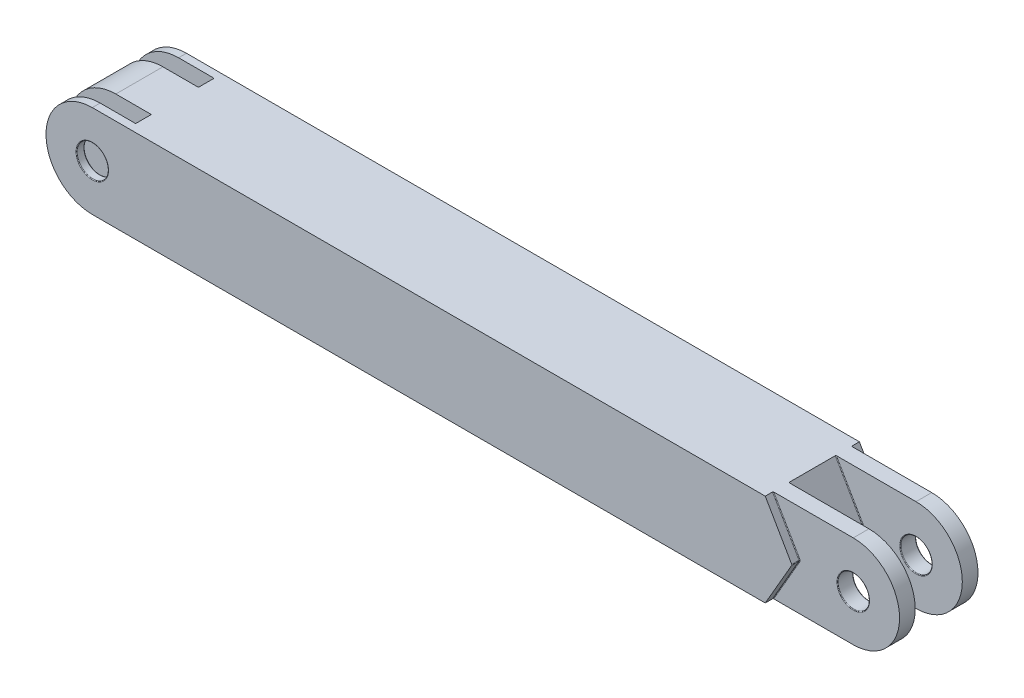
SolidWorks part; units mm, degrees
material "Structural Steel"
ref_plane "Front Plane" through (0, 0, 0) normal (0, 0, 1) x (1, 0, 0)
ref_plane "Top Plane" through (0, 0, 0) normal (0, 1, 0) x (1, 0, 0)
ref_plane "Right Plane" through (0, 0, 0) normal (1, 0, 0) x (0, 0, -1)
sketch "Sketch2" plane through (0, 0, 0) normal (0, 0, 1) x (1, 0, 0)
  line L0 (-3378.4578, 0) -> (441.8552, 0) construction
  line L1 (-2400, 147.5) -> (0, 147.5)
  line L2 (0, -147.5) -> (-2400, -147.5)
  arc A0 (0, 147.5) -> (0, -147.5) centre (0, 0) cw
  arc A1 (-2400, -147.5) -> (-2400, 147.5) centre (-2400, 0) cw
  circle A2 centre (-2400, 0) radius 50
  circle A3 centre (0, 0) radius 50
  dimension "D2" = 147.5
  dimension "D3" = 100
  dimension "D4" = 100
  dimension "D1" = 2400
extrude "Boss-Extrude1" add sketch "Sketch2" along normal mid plane 300
sketch "Sketch4" plane through (0, 0, 0) normal (0, 0, 1) x (1, 0, 0)
  line L0 (-2257.5259, 38.1758) -> (-2286.8193, 147.5)
  line L4 (-3008.6022, 0) -> (749.044, 0) construction
  line L7 (0, 147.5) -> (-2400, 147.5) construction
  line L8 (-2253.0613, 12.8555) -> (-2239.032, -147.5)
  line L9 (-2400, -147.5) -> (0, -147.5) construction
  line L10 (-2286.8193, 147.5) -> (-2400, 147.5)
  line L11 (-2239.032, -147.5) -> (-2400, -147.5)
  arc A0 (-2400, 147.5) -> (-2400, -147.5) centre (-2400, 0) ccw
  arc A1 (-2400, -147.5) -> (-2253.0613, 12.8555) centre (-2400, 0) ccw construction
  arc A2 (-2253.0613, 12.8555) -> (-2257.5259, 38.1758) centre (-2400, 0) ccw
  arc A4 (-2400, 147.5) -> (-2400, -147.5) centre (-2400, 0) ccw construction
  dimension "D1" = 75
  dimension "D2" = 95
extrude "Cut-Extrude1" cut sketch "Sketch4" against normal blind 50 from offset 75 offset against normal yes
mirror "Mirror1" about plane through (0, 0, 0) normal (0, 0, 1) of "Cut-Extrude1"
sketch "Sketch5" plane through (0, 0, 0) normal (0, 0, 1) x (1, 0, 0)
  line L0 (-255.4775, 147.5) -> (-170.3183, 0)
  line L1 (-163.8289, -283.76) -> (104.6936, 181.3346) construction
  line L2 (0, 147.5) -> (-2400, 147.5) construction
  line L4 (-485.1827, 0) -> (365.4599, 0) construction
  line L5 (-170.3183, 0) -> (-255.4775, -147.5)
  line L6 (-2400, -147.5) -> (0, -147.5) construction
  line L7 (-170.3183, 147.5) -> (-170.3183, -147.5) construction
  line L8 (0, 147.5) -> (-255.4775, 147.5)
  line L9 (-255.4775, -147.5) -> (0, -147.5)
  arc A0 (0, -147.5) -> (0, 147.5) centre (0, 0) ccw construction
  arc A3 (0, -147.5) -> (0, 147.5) centre (0, 0) ccw
  dimension "D1" = 147.5
  dimension "D2" = 60
  dimension "D3" = 60
extrude "Cut-Extrude2" cut sketch "Sketch5" against normal mid plane 150
sketch "Sketch6" plane through (0, 0, 150) normal (0, 0, 1) x (1, 0, 0)
  line L4 (-170.3183, 0) -> (-255.4775, -147.5)
  line L5 (0, 147.5) -> (-255.4775, 147.5)
  line L6 (-255.4775, -147.5) -> (0, -147.5)
  line L7 (-170.3183, 0) -> (-255.4775, -147.5)
  line L8 (-255.4775, 147.5) -> (-170.3183, 0)
  line L9 (0, 147.5) -> (-255.4775, 147.5)
  line L10 (-255.4775, -147.5) -> (0, -147.5)
  line L11 (-255.4775, 147.5) -> (-170.3183, 0)
  arc A3 (0, -147.5) -> (0, 147.5) centre (0, 0) ccw
  arc A5 (0, -147.5) -> (0, 147.5) centre (0, 0) ccw
  dimension "D1" = 0
extrude "Cut-Extrude3" cut sketch "Sketch6" against normal blind 25
sketch "Sketch7" plane through (0, 0, -150) normal (0, 0, -1) x (-1, 0, 0)
  line L4 (170.3183, 0) -> (255.4775, 147.5)
  line L5 (0, -147.5) -> (255.4775, -147.5)
  line L6 (255.4775, 147.5) -> (0, 147.5)
  line L7 (170.3183, 0) -> (255.4775, 147.5)
  line L8 (255.4775, -147.5) -> (170.3183, 0)
  line L9 (0, -147.5) -> (255.4775, -147.5)
  line L10 (255.4775, 147.5) -> (0, 147.5)
  line L11 (255.4775, -147.5) -> (170.3183, 0)
  arc A3 (0, 147.5) -> (0, -147.5) centre (0, 0) ccw
  arc A5 (0, 147.5) -> (0, -147.5) centre (0, 0) ccw
  dimension "D1" = 0
extrude "Cut-Extrude4" cut sketch "Sketch7" against normal blind 25
fillet "Fillet2" radius 3 3 edges at (-170.3183, 0, -137.5) (-170.3183, 0, 137.5) (-170.3183, 0, 0)
sketch "Sketch8" plane through (0, 0, 0) normal (0, 0, 1) x (1, 0, 0)
  line L10 (-2224.0891, -146.1927) -> (-2238.1184, 14.1628)
  line L11 (-187.6388, 0) -> (-268.4679, -140)
  line L12 (-2267.2709, 132.5) -> (-264.1377, 132.5)
  line L13 (-264.1377, -132.5) -> (-2225.287, -132.5)
  line L14 (-268.4679, 140) -> (-187.6388, 0)
  line L15 (-187.6388, 0) -> (-264.1377, -132.5)
  line L16 (-264.1377, 132.5) -> (-187.6388, 0)
  line L17 (-2243.0371, 42.0581) -> (-2272.3304, 151.3823)
  line L18 (-2400, -147.5) -> (-255.4775, -147.5) construction
  line L19 (-255.4775, 147.5) -> (-2400, 147.5) construction
  line L20 (-2225.287, -132.5) -> (-2238.1184, 14.1628)
  line L21 (-2243.0371, 42.0581) -> (-2267.2709, 132.5)
  arc A5 (-2238.1184, 14.1628) -> (-2243.0371, 42.0581) centre (-2400, 0) ccw
  arc A6 (-2238.1184, 14.1628) -> (-2243.0371, 42.0581) centre (-2400, 0) ccw
  dimension "D3" = 15
  dimension "D4" = 15
  dimension "D1" = 15
  dimension "D2" = 15
extrude "Cut-Extrude5" cut sketch "Sketch8" against normal mid plane 270
sketch "Sketch9" plane through (0, 0, 0) normal (0, 0, 1) x (1, 0, 0)
  line L6 (-264.1377, 132.5) -> (-2267.2709, 132.5)
  line L7 (-2267.2709, 132.5) -> (-2243.0371, 42.0581)
  line L8 (-2267.2709, 132.5) -> (-2243.0371, 42.0581)
  line L9 (-2225.287, -132.5) -> (-264.1377, -132.5)
  line L10 (-264.1377, -132.5) -> (-187.6388, 0)
  line L11 (-264.1377, -132.5) -> (-187.6388, 0)
  line L12 (-264.1377, 132.5) -> (-2267.2709, 132.5)
  line L13 (-2238.1184, 14.1628) -> (-2225.287, -132.5)
  line L14 (-2238.1184, 14.1628) -> (-2225.287, -132.5)
  line L15 (-2225.287, -132.5) -> (-264.1377, -132.5)
  line L16 (-187.6388, 0) -> (-264.1377, 132.5)
  line L17 (-187.6388, 0) -> (-264.1377, 132.5)
  arc A1 (-2238.1184, 14.1628) -> (-2243.0371, 42.0581) centre (-2400, 0) ccw
  arc A2 (-2238.1184, 14.1628) -> (-2243.0371, 42.0581) centre (-2400, 0) ccw
  dimension "D1" = 0
extrude "Boss-Extrude2" add sketch "Sketch9" along normal mid plane 15
fillet "Fillet1" radius 2 24 edges at (-213.3309, 74.5, -75) (-170.7824, 0, -75) (-213.3309, 74.5, 125) (-170.7824, 0, 125) (-213.3309, 74.5, 75) (-170.7824, 0, 75) (-213.3309, 74.5, -125) (-170.7824, 0, -125) (-213.3309, -74.5, -75) (-213.3309, -74.5, 125) (-213.3309, -74.5, 75) (-213.3309, -74.5, -125) (-2246.0466, -67.3223, 125) (-2254.7409, 25.6131, 125) (-2246.0466, -67.3223, 75) (-2254.7409, 25.6131, 75) (-2246.0466, -67.3223, -75) (-2254.7409, 25.6131, -75) (-2246.0466, -67.3223, -125) (-2254.7409, 25.6131, -125) (-2272.1726, 92.8379, 125) (-2272.1726, 92.8379, 75) (-2272.1726, 92.8379, -75) (-2272.1726, 92.8379, -125)
fillet "Fillet3" radius 2 10 edges at (-50, 0, -125) (50, 0, -75) (50, 0, 125) (50, 0, 75) (-2350, 0, -125) (-2350, 0, -150) (-2350, 0, -75) (-2450, 0, 75) (-2450, 0, 125) (-2350, 0, 150)
fillet "Fillet4" radius 5 38 edges at (-2239.9687, 28.2178, 135) (-2231.7027, -59.1686, 135) (-1265.7043, 132.5, 135) (-1265.7043, 132.5, -7.5) (-2239.9687, 28.2178, -7.5) (-2231.7027, -59.1686, -7.5) (-1265.7043, 132.5, -135) (-2231.7027, -59.1686, -135) (-2239.9687, 28.2178, -135) (-2231.7027, -59.1686, 7.5) (-2239.9687, 28.2178, 7.5) (-1265.7043, 132.5, 7.5) (-2225.287, -132.5, -71.25) (-1244.7124, -132.5, -135) (-1244.7124, -132.5, -7.5) (-1244.7124, -132.5, 135) (-2225.287, -132.5, 71.25) (-1244.7124, -132.5, 7.5) (-225.8883, -66.25, 135) (-264.1377, -132.5, 71.25) (-225.8883, -66.25, 7.5) (-225.8883, 66.25, 135) (-187.6388, 0, 71.25) (-225.8883, 66.25, 7.5) (-264.1377, 132.5, 71.25) (-225.8883, 66.25, -135) (-264.1377, 132.5, -71.25) (-225.8883, 66.25, -7.5) (-264.1377, -132.5, -71.25) (-225.8883, -66.25, -135) (-187.6388, 0, -71.25) (-225.8883, -66.25, -7.5) (-2267.2709, 132.5, -71.25) (-2255.154, 87.279, -135) (-2255.154, 87.279, -7.5) (-2255.154, 87.279, 135) (-2267.2709, 132.5, 71.25) (-2255.154, 87.279, 7.5)
ref_plane "mesh_plane1" [suppressed] through (-267.0245, 0, 0) normal (1, 0, 0) x (0, 0, -1)
ref_plane "mesh_plane2" [suppressed] through (-2220.7054, 0, 0) normal (1, 0, 0) x (0, 0, -1)
split "Split1" [suppressed] bodies to split 109
